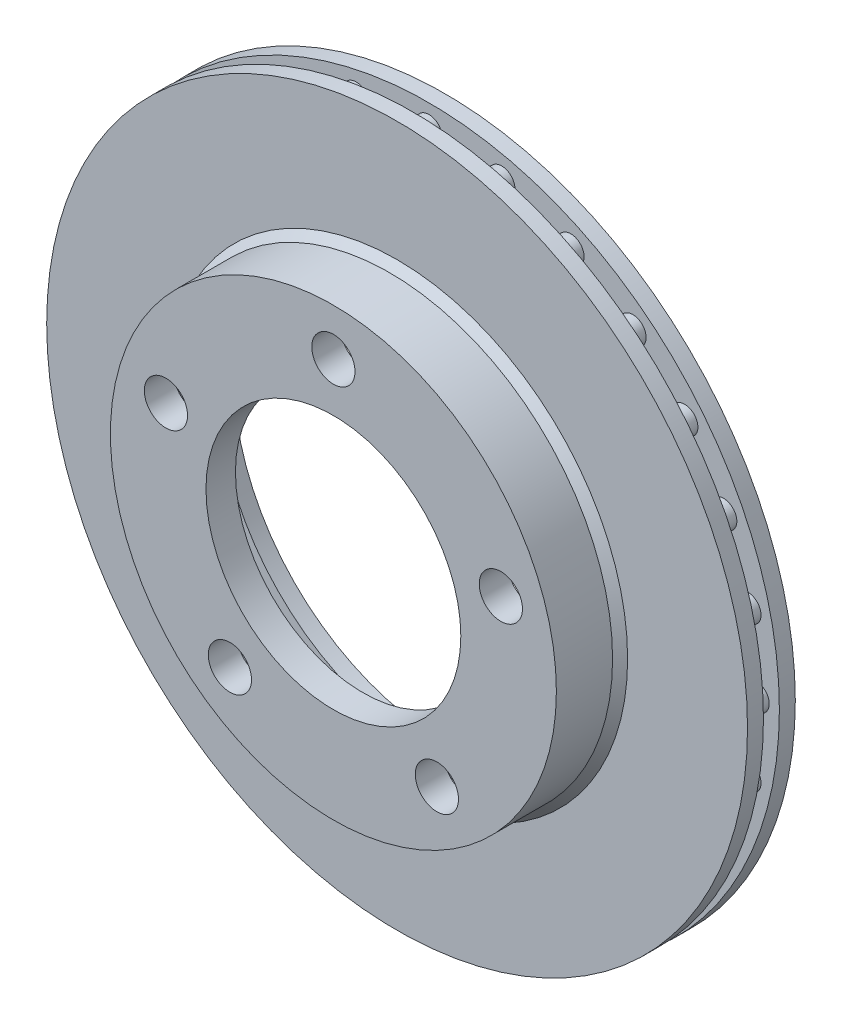
SolidWorks part; units mm, degrees
note: The reader was unsure of these and kept them because the rebuilt part matched: shared geometry of "Sketch1<9>".
ref_plane "Front Plane" through (0, 0, 0) normal (0, 0, 1) x (1, 0, 0)
ref_plane "Top Plane" through (0, 0, 0) normal (0, 1, 0) x (1, 0, 0)
ref_plane "Right Plane" through (0, 0, 0) normal (1, 0, 0) x (0, 0, -1)
sketch "Sketch1" plane through (0, 0, 0) normal (0, 0, 1) x (1, 0, 0)
  circle A0 centre (0, 0) radius 139.7
  circle A1 centre (0, 0) radius 88.9
  circle A2 centre (0, 0) radius 50.8
  circle A3 centre (0, 70.1921) radius 8.6134
  circle A4 centre (66.7567, 21.6906) radius 8.6134
  circle A5 centre (41.2579, -56.7866) radius 8.6134
  circle A6 centre (-41.2579, -56.7866) radius 8.6134
  circle A7 centre (-66.7567, 21.6906) radius 8.6134
  dimension "D1" = 279.4
  dimension "D2" = 177.8
  dimension "D3" = 101.6
  dimension "D4" = 17.2268
  dimension "D5" = 70.1921
extrude "Extrude4" add sketch "Sketch1" against normal blind 6.35
extrude "Extrude5" add sketch "Sketch1<9>" along normal blind 25.4 contours A1 A7 A6 A5 A4 A3 A2
sketch "Sketch1<9>" plane through (0, 0, 0) normal (0, 0, 1) x (1, 0, 0) same geometry as "Sketch1"
chamfer "Chamfer1" distance 3 angle 45 1 edges at (88.9, 0, 0)
sketch "Sketch2" plane through (0, 0, -6.35) normal (0, 0, -1) x (-1, 0, 0)
  circle A0 centre (0, 0) radius 84.2445
extrude "Cut-Extrude1" cut sketch "Sketch2" against normal blind 20
sketch "Sketch3" plane through (0, 0, -6.35) normal (0, 0, -1) x (-1, 0, 0)
  line L0 (5.3067, 130.3469) -> (5.3067, 109.7832)
  line L1 (-5.3067, 130.3469) -> (-5.3067, 109.7832)
  line L2 (34.1786, 125.8979) -> (29.6028, 105.8499)
  line L3 (23.8312, 128.2597) -> (19.2554, 108.2116)
  line L4 (61.3366, 115.136) -> (52.4144, 96.6088)
  line L5 (51.7742, 119.741) -> (42.852, 101.2138)
  line L6 (85.4189, 98.6006) -> (72.5977, 82.5233)
  line L7 (77.121, 105.218) -> (64.2998, 89.1407)
  line L8 (105.218, 77.121) -> (89.1407, 64.2998)
  line L9 (98.6006, 85.4189) -> (82.5233, 72.5977)
  line L10 (119.741, 51.7742) -> (101.2138, 42.852)
  line L11 (115.136, 61.3366) -> (96.6088, 52.4144)
  line L12 (128.2597, 23.8312) -> (108.2116, 19.2554)
  line L13 (125.8979, 34.1786) -> (105.8499, 29.6028)
  line L14 (130.3469, -5.3067) -> (109.7832, -5.3067)
  line L15 (130.3469, 5.3067) -> (109.7832, 5.3067)
  line L16 (125.8979, -34.1786) -> (105.8499, -29.6028)
  line L17 (128.2597, -23.8312) -> (108.2116, -19.2554)
  line L18 (115.136, -61.3366) -> (96.6088, -52.4144)
  line L19 (119.741, -51.7742) -> (101.2138, -42.852)
  line L20 (98.6006, -85.4189) -> (82.5233, -72.5977)
  line L21 (105.218, -77.121) -> (89.1407, -64.2998)
  line L22 (77.121, -105.218) -> (64.2998, -89.1407)
  line L23 (85.4189, -98.6006) -> (72.5977, -82.5233)
  line L24 (51.7742, -119.741) -> (42.852, -101.2138)
  line L25 (61.3366, -115.136) -> (52.4144, -96.6088)
  line L26 (23.8312, -128.2597) -> (19.2554, -108.2116)
  line L27 (34.1786, -125.8979) -> (29.6028, -105.8499)
  line L28 (-5.3067, -130.3469) -> (-5.3067, -109.7832)
  line L29 (5.3067, -130.3469) -> (5.3067, -109.7832)
  line L30 (-34.1786, -125.8979) -> (-29.6028, -105.8499)
  line L31 (-23.8312, -128.2597) -> (-19.2554, -108.2116)
  line L32 (-61.3366, -115.136) -> (-52.4144, -96.6088)
  line L33 (-51.7742, -119.741) -> (-42.852, -101.2138)
  line L34 (-85.4189, -98.6006) -> (-72.5977, -82.5233)
  line L35 (-77.121, -105.218) -> (-64.2998, -89.1407)
  line L36 (-105.218, -77.121) -> (-89.1407, -64.2998)
  line L37 (-98.6006, -85.4189) -> (-82.5233, -72.5977)
  line L38 (-119.741, -51.7742) -> (-101.2138, -42.852)
  line L39 (-115.136, -61.3366) -> (-96.6088, -52.4144)
  line L40 (-128.2597, -23.8312) -> (-108.2116, -19.2554)
  line L41 (-125.8979, -34.1786) -> (-105.8499, -29.6028)
  line L42 (-130.3469, 5.3067) -> (-109.7832, 5.3067)
  line L43 (-130.3469, -5.3067) -> (-109.7832, -5.3067)
  line L44 (-125.8979, 34.1786) -> (-105.8499, 29.6028)
  line L45 (-128.2597, 23.8312) -> (-108.2116, 19.2554)
  line L46 (-115.136, 61.3366) -> (-96.6088, 52.4144)
  line L47 (-119.741, 51.7742) -> (-101.2138, 42.852)
  line L48 (-98.6006, 85.4189) -> (-82.5233, 72.5977)
  line L49 (-105.218, 77.121) -> (-89.1407, 64.2998)
  line L50 (-77.121, 105.218) -> (-64.2998, 89.1407)
  line L51 (-85.4189, 98.6006) -> (-72.5977, 82.5233)
  line L52 (-51.7742, 119.741) -> (-42.852, 101.2138)
  line L53 (-61.3366, 115.136) -> (-52.4144, 96.6088)
  line L54 (-23.8312, 128.2597) -> (-19.2554, 108.2116)
  line L55 (-34.1786, 125.8979) -> (-29.6028, 105.8499)
  arc A0 (5.3067, 130.3469) -> (-5.3067, 130.3469) centre (0, 130.3469) ccw
  arc A1 (-5.3067, 109.7832) -> (5.3067, 109.7832) centre (0, 109.7832) ccw
  arc A2 (19.2554, 108.2116) -> (29.6028, 105.8499) centre (24.4291, 107.0307) ccw
  arc A3 (34.1786, 125.8979) -> (23.8312, 128.2597) centre (29.0049, 127.0788) ccw
  arc A4 (42.852, 101.2138) -> (52.4144, 96.6088) centre (47.6332, 98.9113) ccw
  arc A5 (61.3366, 115.136) -> (51.7742, 119.741) centre (56.5554, 117.4385) ccw
  arc A6 (64.2998, 89.1407) -> (72.5977, 82.5233) centre (68.4487, 85.832) ccw
  arc A7 (85.4189, 98.6006) -> (77.121, 105.218) centre (81.2699, 101.9093) ccw
  arc A8 (82.5233, 72.5977) -> (89.1407, 64.2998) centre (85.832, 68.4487) ccw
  arc A9 (105.218, 77.121) -> (98.6006, 85.4189) centre (101.9093, 81.2699) ccw
  arc A10 (96.6088, 52.4144) -> (101.2138, 42.852) centre (98.9113, 47.6332) ccw
  arc A11 (119.741, 51.7742) -> (115.136, 61.3366) centre (117.4385, 56.5554) ccw
  arc A12 (105.8499, 29.6028) -> (108.2116, 19.2554) centre (107.0307, 24.4291) ccw
  arc A13 (128.2597, 23.8312) -> (125.8979, 34.1786) centre (127.0788, 29.0049) ccw
  arc A14 (109.7832, 5.3067) -> (109.7832, -5.3067) centre (109.7832, 0) ccw
  arc A15 (130.3469, -5.3067) -> (130.3469, 5.3067) centre (130.3469, 0) ccw
  arc A16 (108.2116, -19.2554) -> (105.8499, -29.6028) centre (107.0307, -24.4291) ccw
  arc A17 (125.8979, -34.1786) -> (128.2597, -23.8312) centre (127.0788, -29.0049) ccw
  arc A18 (101.2138, -42.852) -> (96.6088, -52.4144) centre (98.9113, -47.6332) ccw
  arc A19 (115.136, -61.3366) -> (119.741, -51.7742) centre (117.4385, -56.5554) ccw
  arc A20 (89.1407, -64.2998) -> (82.5233, -72.5977) centre (85.832, -68.4487) ccw
  arc A21 (98.6006, -85.4189) -> (105.218, -77.121) centre (101.9093, -81.2699) ccw
  arc A22 (72.5977, -82.5233) -> (64.2998, -89.1407) centre (68.4487, -85.832) ccw
  arc A23 (77.121, -105.218) -> (85.4189, -98.6006) centre (81.2699, -101.9093) ccw
  arc A24 (52.4144, -96.6088) -> (42.852, -101.2138) centre (47.6332, -98.9113) ccw
  arc A25 (51.7742, -119.741) -> (61.3366, -115.136) centre (56.5554, -117.4385) ccw
  arc A26 (29.6028, -105.8499) -> (19.2554, -108.2116) centre (24.4291, -107.0307) ccw
  arc A27 (23.8312, -128.2597) -> (34.1786, -125.8979) centre (29.0049, -127.0788) ccw
  arc A28 (5.3067, -109.7832) -> (-5.3067, -109.7832) centre (0, -109.7832) ccw
  arc A29 (-5.3067, -130.3469) -> (5.3067, -130.3469) centre (0, -130.3469) ccw
  arc A30 (-19.2554, -108.2116) -> (-29.6028, -105.8499) centre (-24.4291, -107.0307) ccw
  arc A31 (-34.1786, -125.8979) -> (-23.8312, -128.2597) centre (-29.0049, -127.0788) ccw
  arc A32 (-42.852, -101.2138) -> (-52.4144, -96.6088) centre (-47.6332, -98.9113) ccw
  arc A33 (-61.3366, -115.136) -> (-51.7742, -119.741) centre (-56.5554, -117.4385) ccw
  arc A34 (-64.2998, -89.1407) -> (-72.5977, -82.5233) centre (-68.4487, -85.832) ccw
  arc A35 (-85.4189, -98.6006) -> (-77.121, -105.218) centre (-81.2699, -101.9093) ccw
  arc A36 (-82.5233, -72.5977) -> (-89.1407, -64.2998) centre (-85.832, -68.4487) ccw
  arc A37 (-105.218, -77.121) -> (-98.6006, -85.4189) centre (-101.9093, -81.2699) ccw
  arc A38 (-96.6088, -52.4144) -> (-101.2138, -42.852) centre (-98.9113, -47.6332) ccw
  arc A39 (-119.741, -51.7742) -> (-115.136, -61.3366) centre (-117.4385, -56.5554) ccw
  arc A40 (-105.8499, -29.6028) -> (-108.2116, -19.2554) centre (-107.0307, -24.4291) ccw
  arc A41 (-128.2597, -23.8312) -> (-125.8979, -34.1786) centre (-127.0788, -29.0049) ccw
  arc A42 (-109.7832, -5.3067) -> (-109.7832, 5.3067) centre (-109.7832, 0) ccw
  arc A43 (-130.3469, 5.3067) -> (-130.3469, -5.3067) centre (-130.3469, 0) ccw
  arc A44 (-108.2116, 19.2554) -> (-105.8499, 29.6028) centre (-107.0307, 24.4291) ccw
  arc A45 (-125.8979, 34.1786) -> (-128.2597, 23.8312) centre (-127.0788, 29.0049) ccw
  arc A46 (-101.2138, 42.852) -> (-96.6088, 52.4144) centre (-98.9113, 47.6332) ccw
  arc A47 (-115.136, 61.3366) -> (-119.741, 51.7742) centre (-117.4385, 56.5554) ccw
  arc A48 (-89.1407, 64.2998) -> (-82.5233, 72.5977) centre (-85.832, 68.4487) ccw
  arc A49 (-98.6006, 85.4189) -> (-105.218, 77.121) centre (-101.9093, 81.2699) ccw
  arc A50 (-72.5977, 82.5233) -> (-64.2998, 89.1407) centre (-68.4487, 85.832) ccw
  arc A51 (-77.121, 105.218) -> (-85.4189, 98.6006) centre (-81.2699, 101.9093) ccw
  arc A52 (-52.4144, 96.6088) -> (-42.852, 101.2138) centre (-47.6332, 98.9113) ccw
  arc A53 (-51.7742, 119.741) -> (-61.3366, 115.136) centre (-56.5554, 117.4385) ccw
  arc A54 (-29.6028, 105.8499) -> (-19.2554, 108.2116) centre (-24.4291, 107.0307) ccw
  arc A55 (-23.8312, 128.2597) -> (-34.1786, 125.8979) centre (-29.0049, 127.0788) ccw
extrude "Extrude6" add sketch "Sketch3" along normal blind 6.35
ref_plane "Plane1" through (0, 0, -12.7) normal (0, 0, -1) x (-1, 0, 0)
sketch "Sketch4" plane through (0, 0, -12.7) normal (0, 0, -1) x (-1, 0, 0)
  circle A0 centre (0, 0) radius 139.7
  circle A1 centre (0, 0) radius 84.2445
extrude "Extrude7" add sketch "Sketch4" along normal blind 6.35
